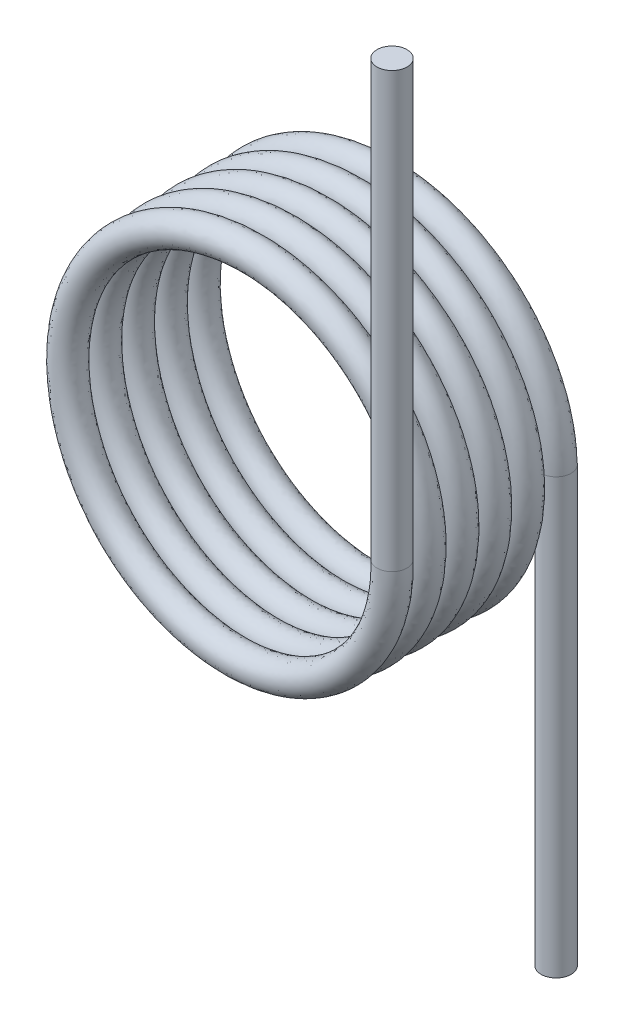
SolidWorks part; units mm, degrees
note: '?' marks a value the reader was unsure of.
ref_plane "Front" through (0, 0, 0) normal (0, 0, 1) x (1, 0, 0)
ref_plane "Top" through (0, 0, 0) normal (0, 1, 0) x (1, 0, 0)
ref_plane "Right" through (0, 0, 0) normal (1, 0, 0) x (0, 0, -1)
sketch "Sketch1" plane through (0, 0, 0) normal (0, 0, 1) x (1, 0, 0)
  circle A0 centre (0, 0) radius 2.55
  circle A1 centre (0, 0) radius 2.25 construction
  circle A2 centre (0, 2.55) radius 0.3 construction
  dimension "D1" = 0.6
  dimension "D2" = 4.5
curve "Helix/Spiral1" pitch 0.4917 height 2.4583 turns 5
sketch "Sketch2" plane through (0, 0, 0) normal (0, 1, 0) x (1, 0, 0)
  circle A0 centre (2.55, 0) radius 0.225
  dimension "D1" = 0.45
sweep "Sweep1" add profiles "Sketch2" path "Helix/Spiral1"
sketch "Sketch4" plane through (0, 0, 0) normal (0, -1, 0) x (1, 0, 0)
  circle A1 centre (2.55, -2.4583) radius 0.225
  circle A2 centre (2.55, -2.4583) radius 0.225
  dimension "D1" = 0
extrude "Boss-Extrude1" add sketch "Sketch4" along normal blind 6.5
sketch "Sketch5" plane through (0, 0, 0) normal (0, 1, 0) x (1, 0, 0)
  circle A1 centre (2.55, 0) radius 0.225
  circle A2 centre (2.55, 0) radius 0.225
  dimension "D1" = 0
extrude "Boss-Extrude2" add sketch "Sketch5" along normal blind 6.5
sketch "Sketch11" plane through (0, 0, 0) normal (1, 0, 0) x (0, 0, -1)
  line L0 (0, 0) -> (2.4583, 0)
  line L2 (1.2292, 0) -> (1.2292, 5.2574)
  line L3 (2.4583, 2.55) -> (2.4583, 0) construction
  line L4 (2.6833, 0) -> (2.2333, 0) construction
ref_plane "Plane1" through (0, 0, -1.2292) normal (0, 0, 1) x (1, 0, 0)
ref_axis "Axis1" through (2.55, 10.4349, 0) along (0, -1, 0)?
ref_axis "Axis3" through (2.55, -0.815, -2.4583) along (0, -1, 0)?
